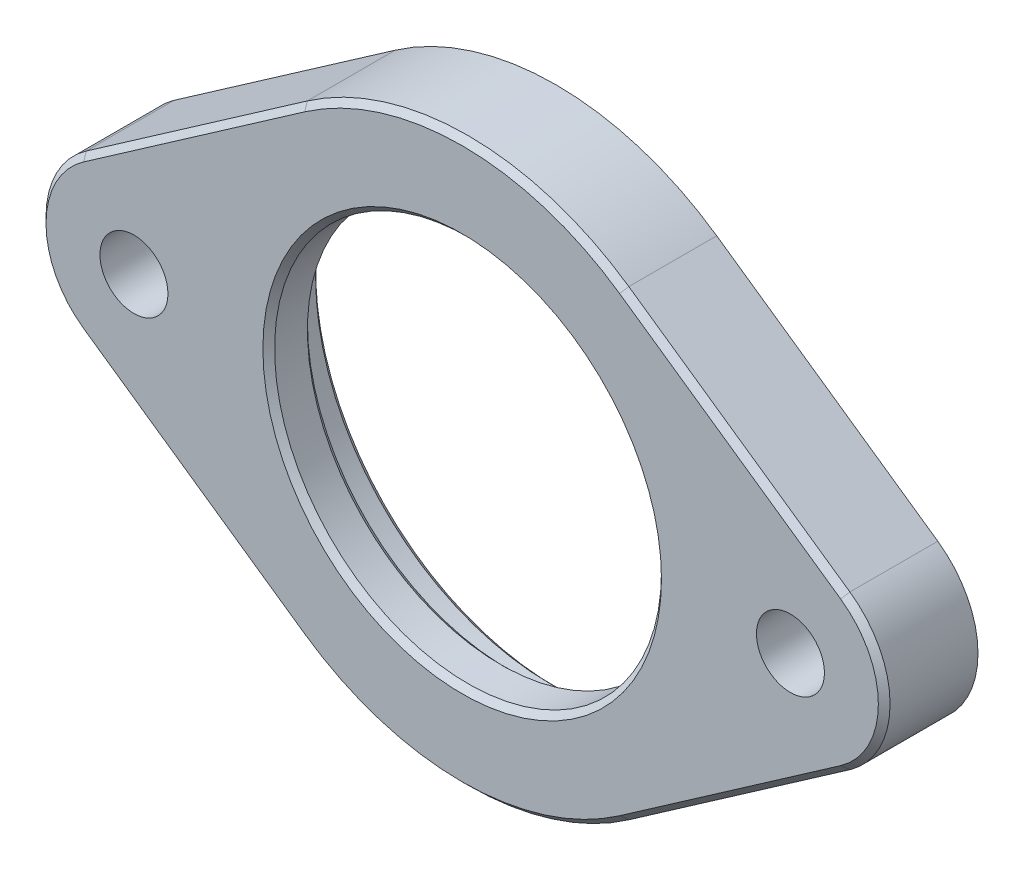
SolidWorks part; units mm, degrees
material "ABS"
ref_plane "Front Plane" through (0, 0, 0) normal (0, 0, 1) x (1, 0, 0)
ref_plane "Top Plane" through (0, 0, 0) normal (0, 1, 0) x (1, 0, 0)
ref_plane "Right Plane" through (0, 0, 0) normal (1, 0, 0) x (0, 0, -1)
sketch "Sketch1" plane through (0, 0, 0) normal (0, 0, 1) x (1, 0, 0)
  line L0 (-14, 0) -> (14, 0)
  line L1 (-6.8571, -9.8478) -> (-16.2857, -3.2826)
  line L2 (-6.8571, 9.8478) -> (-16.2857, 3.2826)
  line L3 (6.8571, 9.8478) -> (16.2857, 3.2826)
  line L4 (6.8571, -9.8478) -> (16.2857, -3.2826)
  circle A0 centre (0, 0) radius 8.25
  circle A1 centre (0, 0) radius 10
  circle A2 centre (0, 0) radius 12
  circle A3 centre (-14, 0) radius 4
  circle A4 centre (14, 0) radius 4
  point P7 (0, 0)
  dimension "D1" = 16.5
  dimension "D2" = 20
  dimension "D3" = 2
  dimension "D4" = 8
  dimension "D5" = 28
extrude "Boss-Extrude1" add sketch "Sketch1" along normal blind 4 contours A3 L0 A2 L2 | A3 L1 A2 L0 | A3 | A4 L3 A2 L0 | A4 | A4 L0 A2 L4 | A2 region at (14.6154, 0, 0) region at (11.8356, 5.4155, 0) region at (11.8356, -5.4155, 0) region at (-14.6154, 0, 0) region at (-11.8356, 5.4155, 0) region at (-11.8356, -5.4155, 0)
extrude "Cut-Extrude1" cut sketch "Sketch1<4>" against normal through all both and the other way through all contours L0 A0 | L0 A0 region at (0, -3.5014, 0) region at (0, 3.5014, 0)
sketch "Sketch1<4>" plane through (0, 0, 0) normal (0, 0, 1) x (1, 0, 0) same geometry as "Sketch1"
extrude "Cut-Extrude2" cut sketch "Sketch1<6>" along normal blind 2.1 and the other way through all contours A1
sketch "Sketch1<6>" plane through (0, 0, 0) normal (0, 0, 1) x (1, 0, 0) same geometry as "Sketch1"
sketch "Sketch2" plane through (0, 0, 4) normal (0, 0, 1) x (1, 0, 0)
  point P0 (-14, 0)
  point P3 (14, 0)
hole_wizard "M2.5 Clearance Hole1" positions "Sketch2" profile "Sketch3" hole size "M2.5" standard "ANSI Metric" end condition through all
sketch "Sketch3" plane through (-14, 0, 4) normal (1, 0, 0) x (0, -1, 0)
  line L0 (0, 0) -> (0, 4)
  line L1 (0, 4) -> (1.45, 4)
  line L2 (1.45, 4) -> (1.45, 0)
  line L5 (1.45, 0) -> (0, 0)
  line L11 (0, -6.35) -> (0, 107.95) construction
  dimension "Thru Hole Dia." = 2.9
  dimension "Thru Hole Depth" = 4
chamfer "Chamfer1" distance 0.25 angle 45 12 edges at (8.25, 0, 4) (8.25, 0, 2.1) (10, 0, 0) (10, 0, 2.1) (0, -12, 4) (11.5714, -6.5652, 4) (-11.5714, -6.5652, 4) (18, 0, 4) (-18, 0, 4) (11.5714, 6.5652, 4) (-11.5714, 6.5652, 4) (0, 12, 4)
